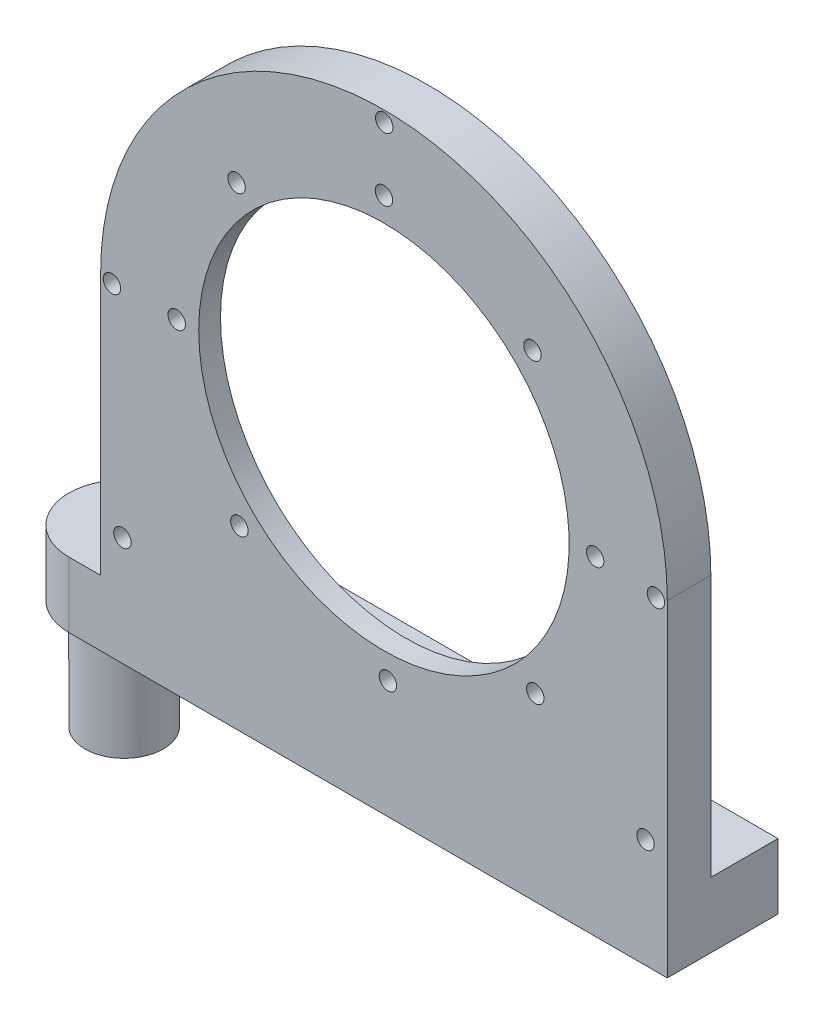
SolidWorks part; units mm, degrees
ref_plane "Front Plane" through (0, 0, 0) normal (0, 0, 1) x (1, 0, 0)
ref_plane "Top Plane" through (0, 0, 0) normal (0, 1, 0) x (1, 0, 0)
ref_plane "Right Plane" through (0, 0, 0) normal (1, 0, 0) x (0, 0, -1)
sketch "Sketch1" plane through (0, 0, 0) normal (0, 1, 0) x (1, 0, 0)
  line L1 (-42.7553, 17.2328) -> (94.5447, 17.2328)
  line L3 (-42.7553, -8.1672) -> (94.5447, -8.1672)
  line L4 (94.5447, 17.2328) -> (94.5447, -8.1672)
  arc A0 (-42.7553, 17.2328) -> (-42.7553, -8.1672) centre (-42.7553, 4.5328) ccw
extrude "Boss-Extrude1" add sketch "Sketch1" along normal blind 15
sketch "Sketch2" plane through (0, 0, 0) normal (0, -1, 0) x (1, 0, 0)
  line L0 (94.5447, -17.2328) -> (-42.7553, -17.2328) construction
  circle A0 centre (-42.7553, -4.5328) radius 9
  arc A1 (-42.7553, 8.1672) -> (-42.7553, -17.2328) centre (-42.7553, -4.5328) ccw construction
  dimension "D1" = 18
  dimension "D2" = 0
  dimension "D3" = 12.7
extrude "Boss-Extrude2" add sketch "Sketch2" along normal blind 25
sketch "Sketch3" plane through (0, 15, 0) normal (0, 1, 0) x (1, 0, 0)
  line L0 (-42.7553, -8.1672) -> (94.5447, -8.1672) construction
  line L1 (94.5447, 17.2328) -> (-35.4553, 17.2328)
  line L2 (94.5447, 17.2328) -> (94.5447, -8.1672)
  line L3 (94.5447, -8.1672) -> (-35.4553, -8.1672)
  line L4 (-35.4553, 17.2328) -> (-35.4553, -8.1672)
  dimension "D1" = 130
extrude "Boss-Extrude4" add sketch "Sketch3" along normal blind 125
sketch "Sketch6" plane through (0, 0, -17.2328) normal (0, 0, -1) x (-1, 0, 0)
  line L1 (-94.5447, 140) -> (35.4553, 140)
  line L2 (-94.5447, 140) -> (-94.5447, 75)
  line L4 (35.4553, 140) -> (35.4553, 75)
  arc A0 (35.4553, 75) -> (-94.5447, 75) centre (-29.5447, 75) ccw
extrude "Cut-Extrude5" cut sketch "Sketch6" against normal blind 150 contours A0 L1 | A0 region at (-20.9364, 125.4811, -17.2328) region at (80.0258, 125.4811, -17.2328)
sketch "Sketch9" plane through (0, 0, -17.2328) normal (0, 0, -1) x (-1, 0, 0)
  line L1 (35.4553, 15) -> (-94.5447, 15)
  line L2 (35.4553, 15) -> (35.4553, 75)
  line L4 (-94.5447, 15) -> (-94.5447, 75)
  arc A0 (35.4553, 75) -> (-94.5447, 75) centre (-29.5447, 75) ccw construction
  arc A1 (35.4553, 75) -> (-94.5447, 75) centre (-29.5447, 75) ccw
extrude "Cut-Extrude6" cut sketch "Sketch9" against normal blind 15.4
sketch "Sketch10" plane through (0, 0, -1.8328) normal (0, 0, -1) x (-1, 0, 0)
  line L0 (35.4553, 15) -> (35.4553, 75) construction
  line L1 (-94.5447, 15) -> (42.7553, 15) construction
  circle A0 centre (-29.5447, 75) radius 60
  dimension "D1" = 65
  dimension "D2" = 60
extrude "Cut-Extrude9" cut sketch "Sketch10" against normal blind 5
sketch "Sketch11" plane through (0, 0, 3.1672) normal (0, 0, -1) x (-1, 0, 0)
  circle A0 centre (-29.5447, 75) radius 42.5
  circle A1 centre (-29.5447, 75) radius 60 construction
  dimension "D1" = 0
extrude "Cut-Extrude10" cut sketch "Sketch11" against normal blind 5
sketch "Sketch12" plane through (0, 0, 3.1672) normal (0, 0, -1) x (-1, 0, 0)
  line L0 (35.4553, 15) -> (35.4553, 75) construction
  circle A0 centre (-29.5447, 123) radius 2
  circle A1 centre (-29.5447, 75) radius 42.5 construction
  circle A3 centre (4.2631, 108.6192) radius 2
  circle A4 centre (18, 74.5447) radius 2
  circle A5 centre (3.6192, 40.7369) radius 2
  circle A6 centre (-30.4553, 27) radius 2
  circle A7 centre (-64.2631, 41.3808) radius 2
  circle A8 centre (-78, 75.4553) radius 2
  circle A9 centre (-63.6192, 109.2631) radius 2
  point P23 (-30, 75)
  dimension "D1" = 48
  dimension "D2" = 65
  dimension "D3" = 8
extrude "Cut-Extrude11" cut sketch "Sketch12" against normal blind 10
sketch "Sketch13" plane through (0, 0, -1.8328) normal (0, 0, -1) x (-1, 0, 0)
  line L0 (-94.5447, 15) -> (42.7553, 15) construction
  line L1 (-94.5447, 75) -> (-94.5447, 15) construction
  circle A0 centre (-89.5447, 25) radius 2
  circle A1 centre (30.4553, 25) radius 2
  dimension "D1" = 10
  dimension "D2" = 5
  dimension "D3" = 2
extrude "Cut-Extrude12" cut sketch "Sketch13" against normal blind 10
sketch "Sketch14" plane through (0, 0, -1.8328) normal (0, 0, -1) x (-1, 0, 0)
  line L0 (-94.5447, 75) -> (-94.5447, 15) construction
  circle A0 centre (-91.9447, 74.2697) radius 2
  circle A1 centre (32.8553, 74.2697) radius 2
  dimension "D1" = 2.6
  dimension "D2" = 2
extrude "Cut-Extrude13" cut sketch "Sketch14" against normal blind 10
sketch "Sketch15" plane through (0, 0, -1.8328) normal (0, 0, -1) x (-1, 0, 0)
  circle A0 centre (-29.6073, 137.5) radius 2
  arc A1 (35.4553, 75) -> (-94.5447, 75) centre (-29.5447, 75) ccw construction
  dimension "D1" = 62.5
extrude "Cut-Extrude14" cut sketch "Sketch15" against normal blind 10
